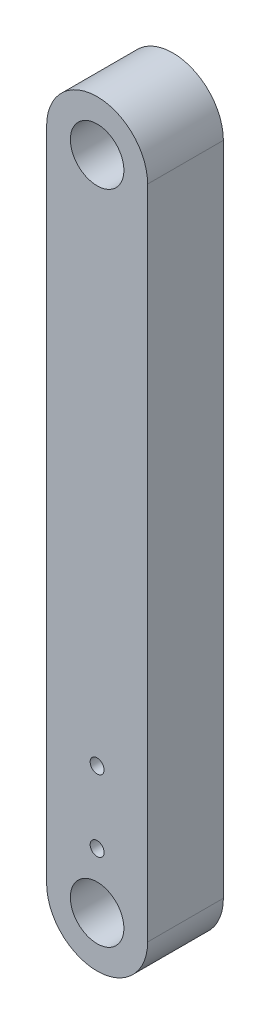
SolidWorks part; units mm, degrees
ref_plane "Front Plane" through (0, 0, 0) normal (0, 0, 1) x (1, 0, 0)
ref_plane "Top Plane" through (0, 0, 0) normal (0, 1, 0) x (1, 0, 0)
ref_plane "Right Plane" through (0, 0, 0) normal (1, 0, 0) x (0, 0, -1)
sketch "Sketch1" plane through (0, 0, 0) normal (0, 0, 1) x (1, 0, 0)
  line L0 (0, 0) -> (0, 82.55) construction
  line L1 (-6.35, 0) -> (-6.35, 82.55)
  line L2 (6.35, 0) -> (6.35, 82.55)
  arc A0 (-6.35, 0) -> (6.35, 0) centre (0, 0) ccw
  arc A1 (6.35, 82.55) -> (-6.35, 82.55) centre (0, 82.55) ccw
  circle A2 centre (0, 82.55) radius 3.3655
  circle A3 centre (0, 0) radius 3.3655
  point P3 (0, 41.275)
  dimension "D2" = 6.35
  dimension "D3" = 6.731
  dimension "D1" = 82.55
extrude "Boss-Extrude1" add sketch "Sketch1" along normal blind 9.525
sketch "Sketch2" plane through (0, 0, 9.525) normal (0, 0, 1) x (1, 0, 0)
  circle A0 centre (0, 7) radius 0.877
  circle A1 centre (0, 16) radius 0.877
  dimension "D3" = 1.754
  dimension "D1" = 7
  dimension "D2" = 16
extrude "Cut-Extrude1" cut sketch "Sketch2" against normal through all
equation "\"tightTol\"= 0.005in"
equation "\"normTol\"= 0.01in"
equation "\"looseTol\"= 0.02in"
equation "\"D3@Sketch1\"=0.25+1.5*\"normTol\""
equation "\"D1@Sketch2\"=7mm"
equation "\"D2@Sketch2\"=16mm"
equation "\"D3@Sketch2\"=1.5mm+\"normTol\""
